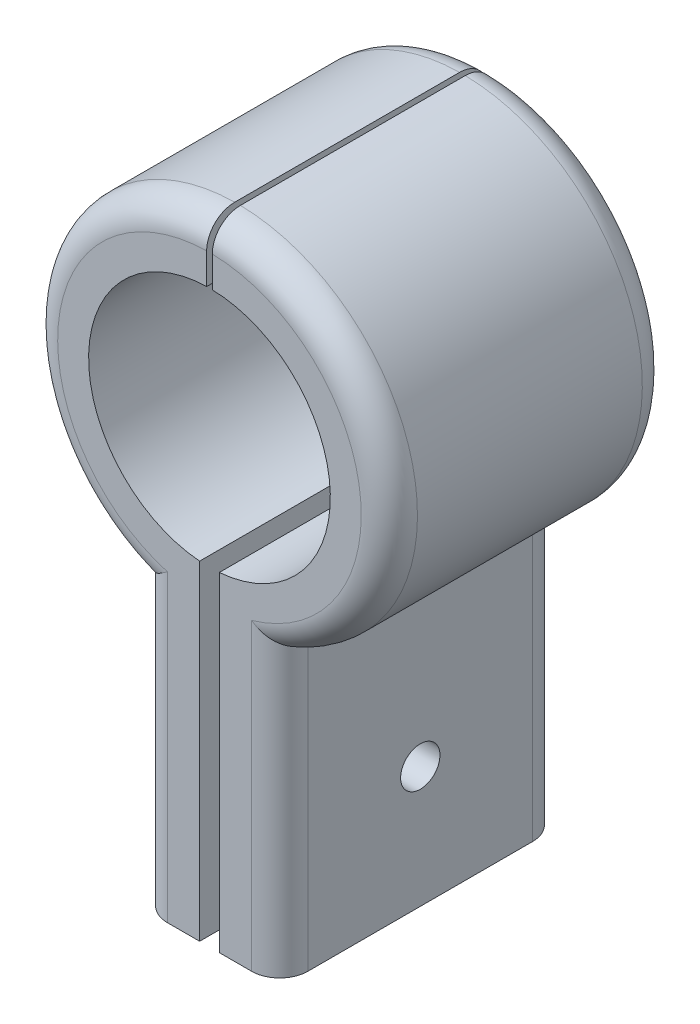
SolidWorks part; units mm, degrees
ref_plane "Front Plane" through (0, 0, 0) normal (0, 0, 1) x (1, 0, 0)
ref_plane "Top Plane" through (0, 0, 0) normal (0, 1, 0) x (1, 0, 0)
ref_plane "Right Plane" through (0, 0, 0) normal (1, 0, 0) x (0, 0, -1)
sketch "Sketch1" plane through (0, 0, 0) normal (0, 0, 1) x (1, 0, 0)
  line L0 (0, -80) -> (0, 0) construction
  line L2 (-12.5, -29.4576) -> (-12.5, -80)
  line L3 (-12.5, -80) -> (-1.75, -80)
  line L4 (12.5, -29.4576) -> (12.5, -80)
  line L5 (-0.5, 21.4942) -> (0.5, 21.4942) construction
  line L7 (-0.5, 31.9961) -> (-0.5, 21.4942)
  line L9 (0.5, 31.9961) -> (0.5, 21.4942)
  line L10 (0, 21.4942) -> (0, 0) construction
  line L11 (-1.75, -21.4287) -> (-1.75, -80)
  line L12 (1.75, -80) -> (1.75, -21.4287)
  line L13 (1.75, -80) -> (12.5, -80)
  line L14 (-1.75, -80) -> (1.75, -80) construction
  arc A0 (-0.5, 21.4942) -> (-1.75, -21.4287) centre (0, 0) ccw
  arc A1 (12.5, -29.4576) -> (0.5, 31.9961) centre (0, 0) ccw
  arc A2 (-0.5, 31.9961) -> (-12.5, -29.4576) centre (0, 0) ccw
  arc A3 (1.75, -21.4287) -> (0.5, 21.4942) centre (0, 0) ccw
  point P16 (0, 0)
  dimension "D1" = 43
  dimension "D2" = 32
  dimension "D3" = 1
  dimension "D4" = 25
  dimension "D5" = 3.5
  dimension "D6" = 80
extrude "Boss-Extrude1" add sketch "Sketch1" along normal mid plane 50
fillet "Fillet1" radius 5 4 edges at (-31.4068, 6.1328, 25) (-31.4068, 6.1328, -25) (-12.5, -54.7288, 25) (-12.5, -54.7288, -25)
fillet "Fillet2" radius 5 4 edges at (31.4068, 6.1328, -25) (12.5, -54.7288, -25) (12.5, -54.7288, 25) (31.4068, 6.1328, 25)
sketch "Sketch3" plane through (-12.5, 0, 0) normal (-1, 0, 0) x (0, 0, 1)
  line L0 (0, 0) -> (0, -58.4496) construction
  circle A0 centre (0, -58.4496) radius 3.5
  dimension "D1" = 7
extrude "Cut-Extrude1" cut sketch "Sketch3" against normal through all both and the other way through all
